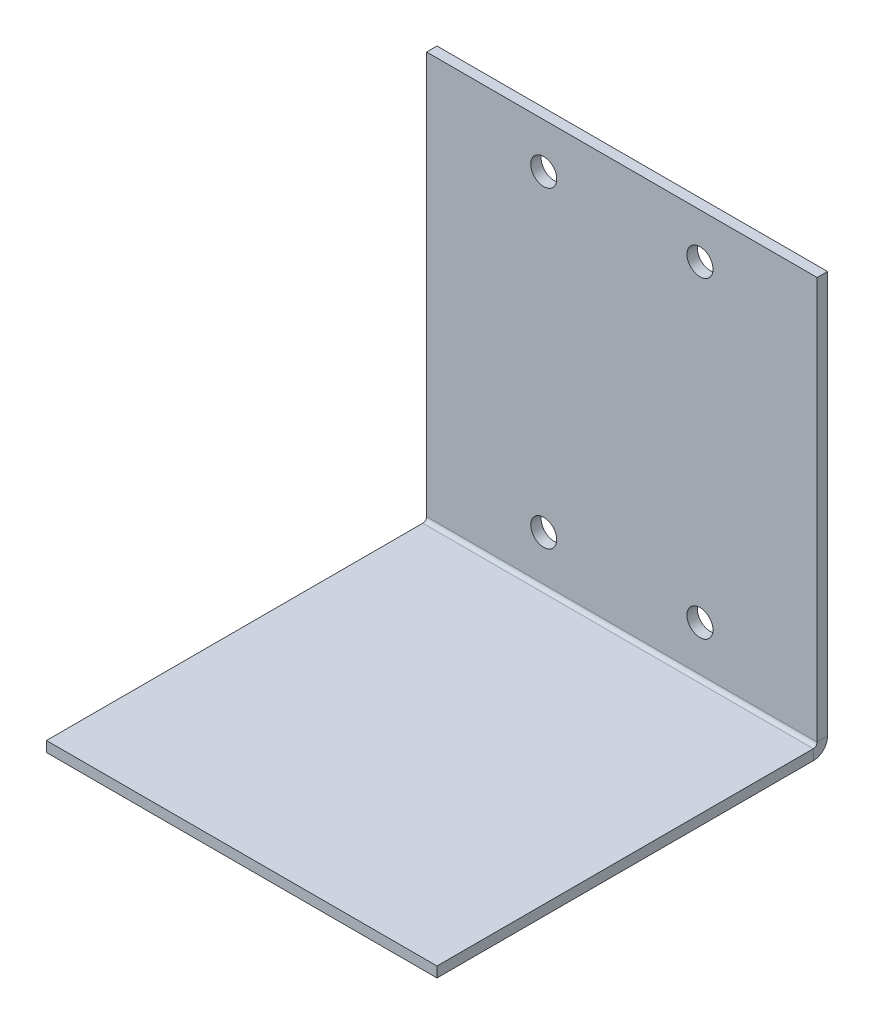
SolidWorks part; units mm, degrees
note: The reader was unsure of these and kept them because the rebuilt part matched: flange length of "Edge-Flange1".
ref_plane "Front Plane" through (0, 0, 0) normal (0, 0, 1) x (1, 0, 0)
ref_plane "Top Plane" through (0, 0, 0) normal (0, 1, 0) x (1, 0, 0)
ref_plane "Right Plane" through (0, 0, 0) normal (1, 0, 0) x (0, 0, -1)
sketch "Sketch2" plane through (0, 0, 0) normal (0, 0, 1) x (1, 0, 0)
  line L1 (0, 0) -> (75, 0)
  line L2 (0, 0) -> (0, 80)
  line L3 (0, 80) -> (75, 80)
  line L4 (75, 0) -> (75, 80)
  dimension "D1" = 80
  dimension "D2" = 75
base flange "Base-Flange1" sketch "Sketch2" thickness 2 reverse thickness direction no parameters "D1"=0.7366
edge flange "Edge-Flange1" sketch "Sketch9" flange angle 90 flange length 75 flange position material inside bend radius 0.7366 thickness 2 relief rectangular parameters "D6"=10
sketch "Sketch9" plane through (0, 0, 0) normal (0, -1, 0) x (1, 0, 0)
  line L0 (0, 0) -> (75, 0) construction
  line L1 (0, 0) -> (75, 0)
  line L2 (0, 0) -> (0, 73)
  line L3 (0, 73) -> (75, 73)
  line L4 (75, 73) -> (75, 0)
bend "EdgeBend1" bend radius 0.7366 bend angle 90 parameters "D5"=1
sketch "Sketch10" plane through (0, 0, -2) normal (0, 0, -1) x (-1, 0, 0)
  line L0 (-75, 80) -> (0, 80) construction
  line L1 (0, 80) -> (0, 2.7366) construction
  line L2 (-75, 41.3683) -> (0, 41.3683) construction
  line L4 (-75, 2.7366) -> (-75, 80) construction
  circle A0 centre (-22.5, 11.37) radius 2.5
  circle A1 centre (-52.5, 71.37) radius 2.5
  circle A2 centre (-52.5, 11.3666) radius 2.5
  circle A3 centre (-22.5, 71.3666) radius 2.5
  dimension "D3" = 5
  dimension "D1" = 60
  dimension "D2" = 30
  dimension "D4" = 8.63
  dimension "D5" = 22.5
extrude "Cut-Extrude1" cut sketch "Sketch10" against normal up to next normal cut yes
sketch "Bend-Lines1" plane through (0, 0, 0) normal (0, 1, 0) x (1, 0, 0)
sketch "Bounding-Box1" plane through (0, 0, 0) normal (0, 1, 0) x (1, 0, 0)
sheet metal parameters "Sheet-Metal1" thickness 2 parameters "D1"=0.7366
flat pattern "Flat-Pattern1" [suppressed]
sketch "Bend-Lines2" plane through (0, 0, 0) normal (0, 1, 0) x (1, 0, 0)
sketch "Bounding-Box2" [suppressed] plane through (0, 0, 0) normal (0, 1, 0) x (1, 0, 0)
sheet metal parameters "Sheet-Metal2" thickness 2 parameters "D1"=0.7366
flat pattern "Flat-Pattern1" [suppressed]
sketch "Bend-Lines2" plane through (0, 0, 0) normal (0, 1, 0) x (1, 0, 0)
sketch "Bounding-Box2" [suppressed] plane through (0, 0, 0) normal (0, 1, 0) x (1, 0, 0)
bend of the flat pattern "Flatten-<EdgeBend1>1"
sheet metal parameters "Sheet-Metal3" thickness 2 parameters "D1"=0.7366
flat pattern "Flat-Pattern1" [suppressed]
sketch "Bend-Lines2" plane through (0, 0, 0) normal (0, 1, 0) x (1, 0, 0)
sketch "Bounding-Box2" [suppressed] plane through (0, 0, 0) normal (0, 1, 0) x (1, 0, 0)
bend of the flat pattern "Flatten-<EdgeBend1>1"
